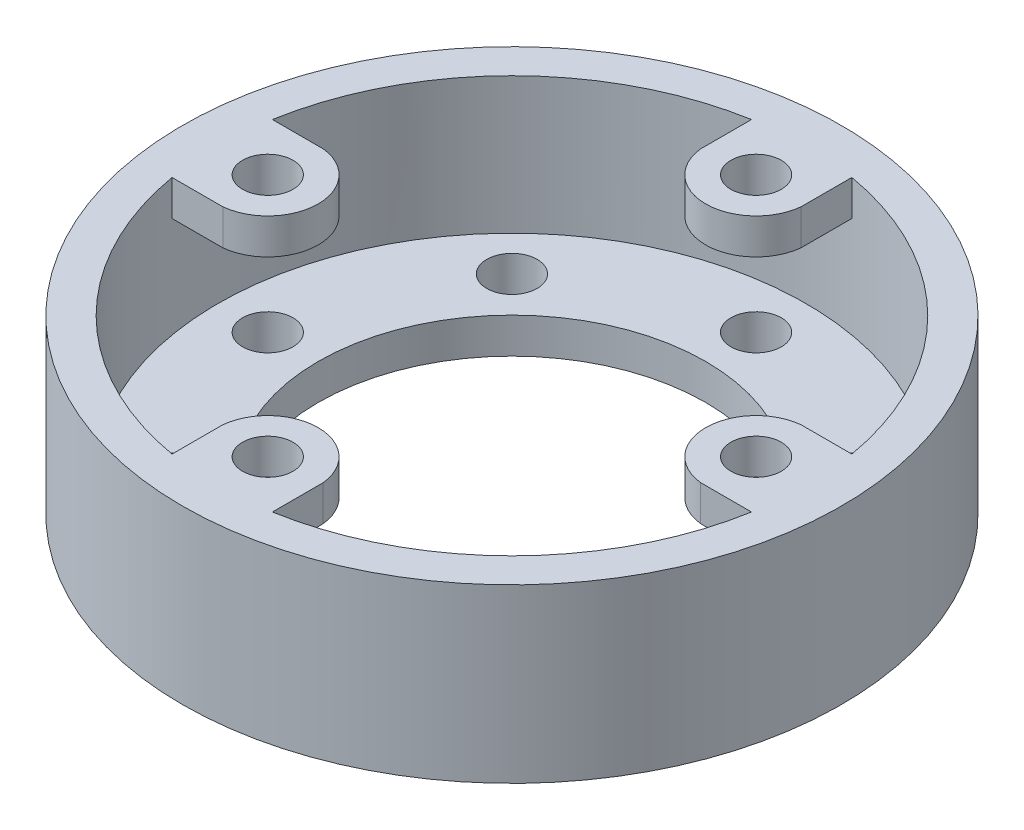
SolidWorks part; units mm, degrees
ref_plane "Front Plane" through (0, 0, 0) normal (0, 0, 1) x (1, 0, 0)
ref_plane "Top Plane" through (0, 0, 0) normal (0, 1, 0) x (1, 0, 0)
ref_plane "Right Plane" through (0, 0, 0) normal (1, 0, 0) x (0, 0, -1)
sketch "Sketch1" plane through (0, 0, 0) normal (0, 1, 0) x (1, 0, 0)
  line L0 (-36.4853, 0) -> (44.8316, 0) construction
  line L1 (0, 38.7507) -> (0, -38.0353) construction
  circle A0 centre (0, 0) radius 28.75
  circle A1 centre (0, 0) radius 16.9
  circle A2 centre (0, 0) radius 25.65
  circle A3 centre (0, 0) radius 21.3 construction
  circle A4 centre (0, 21.3) radius 2.2
  circle A12 centre (15.0614, 15.0614) radius 2.2
  circle A13 centre (21.3, 0) radius 2.2
  circle A14 centre (15.0614, -15.0614) radius 2.2
  circle A15 centre (0, -21.3) radius 2.2
  circle A16 centre (-15.0614, -15.0614) radius 2.2
  circle A17 centre (-21.3, 0) radius 2.2
  circle A18 centre (-15.0614, 15.0614) radius 2.2
  point P12 (15.0608, 15.062)
  point P13 (0, 0)
  point P14 (0, 0)
  dimension "D1" = 57.5
  dimension "D2" = 33.8
  dimension "D3" = 3.1
  dimension "D4" = 42.6
  dimension "D5" = 4.4
  dimension "D6" = 8
extrude "Boss-Extrude1" add sketch "Sketch1" along normal blind 3.1 contours A2 | A1 | A16 | A15 | A14 | A13 | A12 | A4 | A18 | A17
extrude "Boss-Extrude2" add sketch "Sketch1<3>" along normal blind 15 contours A0 | A2
sketch "Sketch1<3>" plane through (0, 0, 0) normal (0, 1, 0) x (1, 0, 0) same geometry as "Sketch1"
ref_plane "Plane1" through (0, 11.9, 0) normal (0, 1, 0) x (1, 0, 0)
sketch "Sketch2" plane through (0, 11.9, 0) normal (0, 1, 0) x (1, 0, 0)
  line L0 (-20.8455, 4.3765) -> (-25.2739, 4.3765)
  line L1 (-20.8455, -4.3765) -> (-25.2739, -4.3765)
  line L2 (-21.3, 0) -> (21.3, 0) construction
  line L3 (0, 21.3) -> (0, -21.3) construction
  line L4 (4.3765, 20.8455) -> (4.3765, 25.2739)
  line L5 (-4.3765, 20.8455) -> (-4.3765, 25.2739)
  line L6 (20.8455, -4.3765) -> (25.2739, -4.3765)
  line L7 (20.8455, 4.3765) -> (25.2739, 4.3765)
  line L8 (-4.3765, -20.8455) -> (-4.3765, -25.2739)
  line L9 (4.3765, -20.8455) -> (4.3765, -25.2739)
  circle A0 centre (-21.3, 0) radius 2.2
  arc A1 (-20.8455, 4.3765) -> (-20.8455, -4.3765) centre (-21.3, 0) cw
  circle A2 centre (0, 0) radius 21.3 construction
  circle A3 centre (0, 0) radius 25.65 construction
  circle A4 centre (0, 21.3) radius 2.2
  arc A6 (4.3765, 20.8455) -> (-4.3765, 20.8455) centre (0, 21.3) cw
  circle A7 centre (21.3, 0) radius 2.2
  arc A8 (20.8455, -4.3765) -> (20.8455, 4.3765) centre (21.3, 0) cw
  circle A9 centre (0, -21.3) radius 2.2
  arc A10 (-4.3765, -20.8455) -> (4.3765, -20.8455) centre (0, -21.3) cw
  circle A11 centre (0, 0) radius 25.65
  point P17 (0, 0)
  point P18 (0, 0)
  point P19 (0, 0)
  dimension "D1" = 4.4
  dimension "D2" = 4.4
  dimension "D4" = 51.3
  dimension "D3" = 4
extrude "Boss-Extrude4" add sketch "Sketch2" along normal blind 3.1 contours L6 A11 L7 A8 A7 | L4 A11 L5 A6 A4 | L8 A11 L9 A10 A9 | L0 A11 L1 A1 A0 region at (-17.0238, 11.9, 0) region at (0, 11.9, -25.5262) region at (-4.2527, 11.9, 23.0597) region at (25.4325, 11.9, -2.1857)
